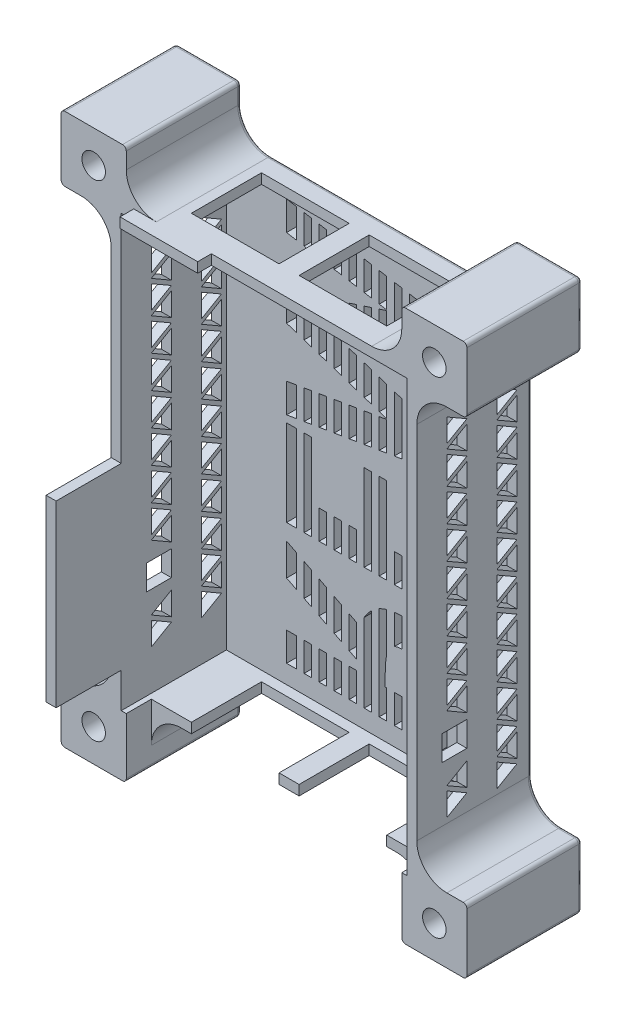
SolidWorks part; units mm, degrees
ref_plane "Front Plane" through (0, 0, 0) normal (0, 0, 1) x (1, 0, 0)
ref_plane "Top Plane" through (0, 0, 0) normal (0, 1, 0) x (1, 0, 0)
ref_plane "Right Plane" through (0, 0, 0) normal (1, 0, 0) x (0, 0, -1)
sketch "Sketch1" plane through (0, 0, 0) normal (0, 0, 1) x (1, 0, 0)
  line L1 (0, 0) -> (61, 0)
  line L2 (0, 0) -> (0, 90)
  line L3 (0, 90) -> (61, 90)
  line L4 (61, 0) -> (61, 90)
  dimension "D1" = 90
  dimension "D2" = 61
extrude "Boss-Extrude1" add sketch "Sketch1" along normal blind 4
sketch "Sketch2" plane through (0, 0, 4) normal (0, 0, 1) x (1, 0, 0)
  line L0 (61, 90) -> (0, 90) construction
  line L1 (2, 88) -> (59, 88)
  line L2 (2, 88) -> (2, 2)
  line L3 (2, 2) -> (59, 2)
  line L4 (59, 88) -> (59, 2)
  line L5 (2.2, 0) -> (-2.2, 0) construction
  line L6 (0, -2.2) -> (0, 2.2) construction
  line L7 (61, 0) -> (61, 90) construction
  dimension "D1" = 2
  dimension "D2" = 2
  dimension "D3" = 2
  dimension "D4" = 2
extrude "Cut-Extrude1" cut sketch "Sketch2" against normal blind 2
sketch "Sketch3" plane through (0, 0, 4) normal (0, 0, 1) x (1, 0, 0)
  line L8 (2, 88) -> (2, 2)
  line L9 (2, 2) -> (59, 2)
  line L10 (59, 2) -> (59, 88)
  line L11 (59, 88) -> (2, 88)
  line L12 (2, 88) -> (2, 2)
  line L13 (2, 2) -> (59, 2)
  line L14 (59, 2) -> (59, 88)
  line L15 (59, 88) -> (2, 88)
  line L26 (0, 90) -> (0, 0)
  line L27 (0, 0) -> (61, 0)
  line L28 (61, 0) -> (61, 90)
  line L29 (61, 90) -> (0, 90)
  line L30 (0, 90) -> (0, 0)
  line L31 (0, 0) -> (61, 0)
  line L32 (61, 0) -> (61, 90)
  line L33 (61, 90) -> (0, 90)
  dimension "D1" = 2
  dimension "D2" = 0
extrude "Boss-Extrude2" add sketch "Sketch3" along normal blind 14
sketch "Sketch4" plane through (0, 0, 18) normal (0, 0, 1) x (1, 0, 0)
  line L2 (9.9, 0) -> (-9.9, 0) construction
  line L3 (0, -9.9) -> (0, 9.9) construction
  line L4 (61, 0) -> (61, 90) construction
  line L10 (0, 90) -> (0, 0) construction
  line L12 (2, 88) -> (2, 2) construction
  line L13 (2, 88) -> (2, 2) construction
  line L14 (2, 2) -> (2, 88)
  line L15 (59, 88) -> (2, 88) construction
  line L16 (59, 88) -> (2, 88) construction
  line L49 (59, 88) -> (2, 88)
  line L50 (59, 2) -> (59, 88)
  line L52 (0, 90) -> (0, 2)
  line L53 (61, 90) -> (0, 90)
  line L54 (61, 2) -> (61, 90)
  line L55 (59, 2) -> (61, 2)
  line L56 (2, 2) -> (0, 2)
  dimension "D2" = 2
  dimension "D3" = 2
  dimension "D1" = 2
extrude "Boss-Extrude3" add sketch "Sketch4" along normal blind 5
sketch "Sketch5" plane through (0, 0, 0) normal (0, -1, 0) x (-1, 0, 0)
  line L0 (0, -18) -> (-61, -18) construction
  line L1 (-11, -18) -> (-28.5, -18)
  line L2 (-11, -18) -> (-11, -4)
  line L3 (-11, -4) -> (-28.5, -4)
  line L4 (-28.5, -18) -> (-28.5, -4)
  line L5 (0, 9.9) -> (0, -9.9) construction
  line L6 (-32.5, -18) -> (-50, -18)
  line L7 (-32.5, -18) -> (-32.5, -4)
  line L8 (-32.5, -4) -> (-50, -4)
  line L9 (-50, -18) -> (-50, -4)
  dimension "D1" = 14
  dimension "D2" = 14
  dimension "D3" = 17.5
  dimension "D4" = 17.5
  dimension "D5" = 4
  dimension "D6" = 11
extrude "Cut-Extrude2" cut sketch "Sketch5" against normal blind 5
sketch "Sketch6" plane through (0, 90, 0) normal (0, 1, 0) x (1, 0, 0)
  line L2 (50, -18) -> (50, -4)
  line L3 (50, -4) -> (32.5, -4)
  line L4 (32.5, -18) -> (32.5, -4)
  line L5 (61, 0) -> (0, 0) construction
  line L7 (28.5, -18) -> (28.5, -4)
  line L8 (28.5, -4) -> (11, -4)
  line L9 (11, -18) -> (11, -4)
  line L10 (61, -23) -> (61, 0) construction
  line L12 (11, -18) -> (28.5, -18)
  line L13 (32.5, -18) -> (50, -18)
  dimension "D1" = 4
  dimension "D2" = 4
  dimension "D3" = 4
  dimension "D4" = 17.5
  dimension "D5" = 17.5
  dimension "D6" = 11
  dimension "D7" = 14
  dimension "D8" = 14
extrude "Cut-Extrude3" cut sketch "Sketch6" against normal blind 5
sketch "Sketch7" plane through (0, 0, 23) normal (0, 0, 1) x (1, 0, 0)
  line L0 (0, 90) -> (0, 2) construction
  line L1 (0, 9) -> (2, 9)
  line L2 (0, 9) -> (0, 44.75)
  line L3 (0, 44.75) -> (2, 44.75)
  line L4 (2, 9) -> (2, 44.75)
  line L5 (2, 2) -> (2, 88) construction
  line L6 (0, 2) -> (2, 2) construction
  dimension "D1" = 7
  dimension "D2" = 35.75
extrude "Boss-Extrude4" add sketch "Sketch7" along normal blind 13
sketch "Sketch8" plane through (61, 0, 0) normal (1, 0, 0) x (0, 0, -1)
  line L0 (-13, 17.852) -> (-13, 13.2332)
  line L5 (-13, 13.2332) -> (-17, 15.5426)
  line L6 (-17, 15.5426) -> (-13, 17.852)
  line L8 (-13, 20) -> (-18, 20)
  line L9 (-13, 20) -> (-13, 25)
  line L10 (-13, 25) -> (-18, 25)
  line L11 (-18, 20) -> (-18, 25)
  line L23 (-18, 0) -> (0, 0) construction
  line L24 (0, 0) -> (0, 90) construction
  line L25 (-3, 12.3094) -> (-7, 10)
  line L26 (-7, 10) -> (-7, 14.6188)
  line L27 (-7, 14.6188) -> (-3, 12.3094)
  line L28 (-3, 13.2332) -> (-7, 15.5426)
  line L29 (-7, 15.5426) -> (-3, 17.852)
  line L30 (-3, 17.852) -> (-3, 13.2332)
  line L31 (-17, 14.6188) -> (-13, 12.3094)
  line L32 (-13, 12.3094) -> (-17, 10)
  line L33 (-17, 10) -> (-17, 14.6188)
  line L40 (-13, 30.7846) -> (-13, 26.1658)
  line L41 (-13, 26.1658) -> (-17, 28.4752)
  line L42 (-17, 28.4752) -> (-13, 30.7846)
  line L46 (-13, 37.2509) -> (-13, 32.6321)
  line L47 (-13, 32.6321) -> (-17, 34.9415)
  line L48 (-17, 34.9415) -> (-13, 37.2509)
  line L49 (-17, 34.0178) -> (-13, 31.7084)
  line L50 (-13, 31.7084) -> (-17, 29.399)
  line L51 (-17, 29.399) -> (-17, 34.0178)
  line L52 (-13, 43.7173) -> (-13, 39.0985)
  line L53 (-13, 39.0985) -> (-17, 41.4079)
  line L54 (-17, 41.4079) -> (-13, 43.7173)
  line L55 (-17, 40.4841) -> (-13, 38.1747)
  line L56 (-13, 38.1747) -> (-17, 35.8653)
  line L57 (-17, 35.8653) -> (-17, 40.4841)
  line L58 (-13, 50.1836) -> (-13, 45.5648)
  line L59 (-13, 45.5648) -> (-17, 47.8742)
  line L60 (-17, 47.8742) -> (-13, 50.1836)
  line L61 (-17, 46.9504) -> (-13, 44.641)
  line L62 (-13, 44.641) -> (-17, 42.3316)
  line L63 (-17, 42.3316) -> (-17, 46.9504)
  line L64 (-13, 56.6499) -> (-13, 52.0311)
  line L65 (-13, 52.0311) -> (-17, 54.3405)
  line L66 (-17, 54.3405) -> (-13, 56.6499)
  line L67 (-17, 53.4167) -> (-13, 51.1073)
  line L68 (-13, 51.1073) -> (-17, 48.7979)
  line L69 (-17, 48.7979) -> (-17, 53.4167)
  line L70 (-13, 63.1162) -> (-13, 58.4974)
  line L71 (-13, 58.4974) -> (-17, 60.8068)
  line L72 (-17, 60.8068) -> (-13, 63.1162)
  line L73 (-17, 59.8831) -> (-13, 57.5737)
  line L74 (-13, 57.5737) -> (-17, 55.2643)
  line L75 (-17, 55.2643) -> (-17, 59.8831)
  line L76 (-13, 69.5825) -> (-13, 64.9637)
  line L77 (-13, 64.9637) -> (-17, 67.2731)
  line L78 (-17, 67.2731) -> (-13, 69.5825)
  line L79 (-17, 66.3494) -> (-13, 64.04)
  line L80 (-13, 64.04) -> (-17, 61.7306)
  line L81 (-17, 61.7306) -> (-17, 66.3494)
  line L82 (-13, 76.0489) -> (-13, 71.4301)
  line L83 (-13, 71.4301) -> (-17, 73.7395)
  line L84 (-17, 73.7395) -> (-13, 76.0489)
  line L85 (-17, 72.8157) -> (-13, 70.5063)
  line L86 (-13, 70.5063) -> (-17, 68.1969)
  line L87 (-17, 68.1969) -> (-17, 72.8157)
  line L91 (-17, 79.282) -> (-13, 76.9726)
  line L92 (-13, 76.9726) -> (-17, 74.6632)
  line L93 (-17, 74.6632) -> (-17, 79.282)
  line L94 (-3, 24.3183) -> (-3, 19.6995)
  line L95 (-3, 19.6995) -> (-7, 22.0089)
  line L96 (-7, 22.0089) -> (-3, 24.3183)
  line L97 (-7, 21.0851) -> (-3, 18.7757)
  line L98 (-3, 18.7757) -> (-7, 16.4663)
  line L99 (-7, 16.4663) -> (-7, 21.0851)
  line L100 (-3, 30.7846) -> (-3, 26.1658)
  line L101 (-3, 26.1658) -> (-7, 28.4752)
  line L102 (-7, 28.4752) -> (-3, 30.7846)
  line L103 (-7, 27.5514) -> (-3, 25.242)
  line L104 (-3, 25.242) -> (-7, 22.9326)
  line L105 (-7, 22.9326) -> (-7, 27.5514)
  line L106 (-3, 37.2509) -> (-3, 32.6321)
  line L107 (-3, 32.6321) -> (-7, 34.9415)
  line L108 (-7, 34.9415) -> (-3, 37.2509)
  line L109 (-7, 34.0178) -> (-3, 31.7084)
  line L110 (-3, 31.7084) -> (-7, 29.399)
  line L111 (-7, 29.399) -> (-7, 34.0178)
  line L112 (-3, 43.7173) -> (-3, 39.0985)
  line L113 (-3, 39.0985) -> (-7, 41.4079)
  line L114 (-7, 41.4079) -> (-3, 43.7173)
  line L115 (-7, 40.4841) -> (-3, 38.1747)
  line L116 (-3, 38.1747) -> (-7, 35.8653)
  line L117 (-7, 35.8653) -> (-7, 40.4841)
  line L118 (-3, 50.1836) -> (-3, 45.5648)
  line L119 (-3, 45.5648) -> (-7, 47.8742)
  line L120 (-7, 47.8742) -> (-3, 50.1836)
  line L121 (-7, 46.9504) -> (-3, 44.641)
  line L122 (-3, 44.641) -> (-7, 42.3316)
  line L123 (-7, 42.3316) -> (-7, 46.9504)
  line L124 (-3, 56.6499) -> (-3, 52.0311)
  line L125 (-3, 52.0311) -> (-7, 54.3405)
  line L126 (-7, 54.3405) -> (-3, 56.6499)
  line L127 (-7, 53.4167) -> (-3, 51.1073)
  line L128 (-3, 51.1073) -> (-7, 48.7979)
  line L129 (-7, 48.7979) -> (-7, 53.4167)
  line L130 (-3, 63.1162) -> (-3, 58.4974)
  line L131 (-3, 58.4974) -> (-7, 60.8068)
  line L132 (-7, 60.8068) -> (-3, 63.1162)
  line L133 (-7, 59.8831) -> (-3, 57.5737)
  line L134 (-3, 57.5737) -> (-7, 55.2643)
  line L135 (-7, 55.2643) -> (-7, 59.8831)
  line L136 (-3, 69.5825) -> (-3, 64.9637)
  line L137 (-3, 64.9637) -> (-7, 67.2731)
  line L138 (-7, 67.2731) -> (-3, 69.5825)
  line L139 (-7, 66.3494) -> (-3, 64.04)
  line L140 (-3, 64.04) -> (-7, 61.7306)
  line L141 (-7, 61.7306) -> (-7, 66.3494)
  line L142 (-3, 76.0489) -> (-3, 71.4301)
  line L143 (-3, 71.4301) -> (-7, 73.7395)
  line L144 (-7, 73.7395) -> (-3, 76.0489)
  line L145 (-7, 72.8157) -> (-3, 70.5063)
  line L146 (-3, 70.5063) -> (-7, 68.1969)
  line L147 (-7, 68.1969) -> (-7, 72.8157)
  line L151 (-7, 79.282) -> (-3, 76.9726)
  line L152 (-3, 76.9726) -> (-7, 74.6632)
  line L153 (-7, 74.6632) -> (-7, 79.282)
  line L154 (-13, 18.7757) -> (-17, 16.4663) [skipped]
  line L155 (-17, 21.0851) -> (-15.1205, 20) [skipped]
  line L156 (-17, 20) -> (-17, 21.0851) [skipped]
  line L157 (-17, 22.0089) -> (-13, 24.3183) [skipped]
  line L158 (-13, 19.6995) -> (-13.5205, 20) [skipped]
  line L159 (-17, 27.5514) -> (-13, 25.242) [skipped]
  line L160 (-13, 25.242) -> (-13.4192, 25) [skipped]
  line L161 (-17, 25) -> (-17, 27.5514) [skipped]
  line L162 (-13, 18.7757) -> (-13, 17.5514) [skipped]
  line L163 (-13, 82.5152) -> (-13, 77.8964) [skipped]
  line L164 (-17, 80.2058) -> (-13, 82.5152) [skipped]
  line L165 (-13, 77.8964) -> (-17, 80.2058) [skipped]
  line L166 (-7, 80.2058) -> (-3, 82.5152) [skipped]
  line L167 (-3, 77.8964) -> (-7, 80.2058) [skipped]
  line L168 (-3, 82.5152) -> (-3, 77.8964) [skipped]
  dimension "D1" = 20
  dimension "D2" = 60
  dimension "D3" = 60
  dimension "D4" = 4
  dimension "D5" = 5
  dimension "D6" = 5
  dimension "D7" = 13
  dimension "D8" = 0.9238
  dimension "D9" = 10
  dimension "D10" = 3
  dimension "D11" = 60
  dimension "D12" = 2
  dimension "D13" = 11
  dimension "D14" = 0.9238
  dimension "D15" = 17
extrude "Cut-Extrude4" cut sketch "Sketch8" against normal through all
sketch "Sketch9" plane through (-13.2665, 62.4944, 0) normal (0, 0, -1) x (0, 1, 0)
  line L2 (-42.6944, 13.2665) -> (-82.2944, 13.2665) construction
  line L3 (-62.4944, -6.5335) -> (-62.4944, 33.0665) construction
  text T0 "REM" font "Century Gothic" height 32
  dimension "D1" = 14
  dimension "D2" = 2
extrude "Cut-Extrude5" cut sketch "Sketch9" against normal blind 2
sketch "Sketch16" plane through (0, 0, 23) normal (0, 0, 1) x (1, 0, 0)
  line L0 (2, 88) -> (59, 88) construction
  line L1 (20, 88) -> (4.5, 88)
  line L2 (20, 88) -> (20, 90)
  line L3 (20, 90) -> (4.5, 90)
  line L4 (4.5, 88) -> (4.5, 90)
  line L5 (61, 90) -> (0, 90) construction
  line L6 (0, 90) -> (0, 61) construction
  dimension "D1" = 4.5
  dimension "D2" = 15.5
extrude "Boss-Extrude9" add sketch "Sketch16" along normal blind 2.75
ref_plane "Plane1" through (2, 14.6188, 17) normal (0, 1, 0) x (1, 0, 0)
sketch "Sketch22" plane through (0, 0, 0) normal (0, 0, -1) x (-1, 0, 0)
  line L0 (-14, 85.9795) -> (-14, 80.1654) construction
  line L1 (-26.5, 0) -> (-25, 0)
  line L2 (0, 0) -> (-61, 0) construction
  line L3 (-61, 90) -> (0, 90) construction
  line L4 (-28, 0) -> (-28, 90)
  line L5 (-28, 90) -> (-29.5, 90)
  line L6 (-29.5, 90) -> (-29.5, 0)
  line L7 (-29.5, 0) -> (-28, 0)
  line L8 (-25, 0) -> (-25, 90)
  line L9 (-25, 90) -> (-26.5, 90)
  line L10 (-26.5, 90) -> (-26.5, 0)
  line L11 (-23.5, 0) -> (-22, 0)
  line L12 (-22, 0) -> (-22, 90)
  line L13 (-22, 90) -> (-23.5, 90)
  line L14 (-23.5, 90) -> (-23.5, 0)
  line L15 (-20.5, 0) -> (-19, 0)
  line L16 (-19, 0) -> (-19, 90)
  line L17 (-19, 90) -> (-20.5, 90)
  line L18 (-20.5, 90) -> (-20.5, 0)
  line L19 (-17.5, 0) -> (-16, 0)
  line L20 (-16, 0) -> (-16, 90)
  line L21 (-16, 90) -> (-17.5, 90)
  line L22 (-17.5, 90) -> (-17.5, 0)
  line L23 (-32.5, 0) -> (-31, 0)
  line L24 (-31, 0) -> (-31, 90)
  line L25 (-31, 90) -> (-32.5, 90)
  line L26 (-32.5, 90) -> (-32.5, 0)
  line L27 (-35.5, 0) -> (-34, 0)
  line L28 (-34, 0) -> (-34, 90)
  line L29 (-34, 90) -> (-35.5, 90)
  line L30 (-35.5, 90) -> (-35.5, 0)
  line L31 (-38.5, 0) -> (-37, 0)
  line L32 (-37, 0) -> (-37, 90)
  line L33 (-37, 90) -> (-38.5, 90)
  line L34 (-38.5, 90) -> (-38.5, 0)
  line L35 (-41.5, 0) -> (-40, 0)
  line L36 (-40, 0) -> (-40, 90)
  line L37 (-40, 90) -> (-41.5, 90)
  line L38 (-41.5, 90) -> (-41.5, 0)
  line L39 (-44.5, 0) -> (-43, 0)
  line L40 (-43, 0) -> (-43, 90)
  line L41 (-43, 90) -> (-44.5, 90)
  line L42 (-44.5, 90) -> (-44.5, 0)
  line L43 (-47.5, 0) -> (-46, 0)
  line L44 (-46, 0) -> (-46, 90)
  line L45 (-46, 90) -> (-47.5, 90)
  line L46 (-47.5, 90) -> (-47.5, 0)
  line L47 (-50.5, 0) -> (-49, 0)
  line L48 (-49, 0) -> (-49, 90)
  line L49 (-49, 90) -> (-50.5, 90)
  line L50 (-50.5, 90) -> (-50.5, 0)
  dimension "D2" = 1.5
  dimension "D4" = 1.5
  dimension "D6" = 1.5
  dimension "D1" = 2
  dimension "D3" = 5
  dimension "D5" = 8
extrude "Boss-Extrude11" add sketch "Sketch22" against normal up to surface (2 mm away) up to face at (36.3205, 13.9436, 2)
fillet "Fillet5" radius 0.75 8 edges at (30.5, 90, 0) (0, 90, 11.5) (30.5, 0, 0) (0, 45, 0) (0, 0, 9) (61, 90, 11.5) (61, 0, 9) (61, 45, 0)
sketch "Sketch36" plane through (0, 0, 0) normal (0, 0, -1) x (-1, 0, 0)
  line L0 (-61, 0.75) -> (-61, 89.25) construction
  line L1 (-58, 3) -> (-71, 3)
  line L2 (-58, 3) -> (-58, -10)
  line L3 (-58, -10) -> (-71, -10)
  line L4 (-71, 3) -> (-71, -10)
  line L5 (-58, 3) -> (-71, -10) construction
  line L6 (-58, -10) -> (-71, 3) construction
  line L8 (-0.75, 0) -> (-60.25, 0) construction
  point P4 (-64.5, -3.5)
  dimension "D1" = 13
  dimension "D2" = 13
  dimension "D3" = 3
  dimension "D4" = 3
extrude "Boss-Extrude13" add sketch "Sketch36" against normal up to surface (23 mm away) up to face at (48.6293, 64.2008, 23)
sketch "Sketch37" plane through (0, 0, 0) normal (0, 0, -1) x (-1, 0, 0)
  line L0 (-60.25, 90) -> (-0.75, 90) construction
  line L1 (-3, 87) -> (10, 87)
  line L2 (-3, 87) -> (-3, 100)
  line L3 (-3, 100) -> (10, 100)
  line L4 (10, 87) -> (10, 100)
  line L5 (-3, 87) -> (10, 100) construction
  line L6 (-3, 100) -> (10, 87) construction
  line L7 (0, 89.25) -> (0, 0.75) construction
  point P4 (3.5, 93.5)
  dimension "D1" = 13
  dimension "D2" = 3
  dimension "D3" = 3
extrude "Boss-Extrude14" add sketch "Sketch37" against normal up to surface (23 mm away) up to face at (1.9421, 76.415, 23)
sketch "Sketch41" plane through (0, 0, 23) normal (0, 0, 1) x (1, 0, 0)
  line L9 (58, 3) -> (59, 3)
  line L10 (58, 3) -> (58, 2)
  line L11 (58, 2) -> (59, 2)
  line L12 (59, 3) -> (59, 2)
  line L13 (58, 3) -> (59, 2) construction
  line L14 (58, 2) -> (59, 3) construction
  line L15 (3, 87) -> (2, 87)
  line L16 (3, 87) -> (3, 88)
  line L17 (3, 88) -> (2, 88)
  line L18 (2, 87) -> (2, 88)
  line L19 (3, 87) -> (2, 88) construction
  line L20 (3, 88) -> (2, 87) construction
  point P13 (58.5, 2.5)
  point P15 (2.5, 87.5)
  dimension "D1" = 1
  dimension "D2" = 1
  dimension "D3" = 1
  dimension "D4" = 1
extrude "Cut-Extrude13" cut sketch "Sketch41" against normal up to surface (21 mm away) up to face at (30.5, 45, 2)
sketch "Sketch46" plane through (0, 0, 0) normal (0, 0, -1) x (-1, 0, 0)
  line L0 (3.5, 100) -> (3.5, 87) construction
  line L1 (10, 100) -> (-3, 100) construction
  line L2 (-0.75, 87) -> (10, 87) construction
  line L3 (10, 93.5) -> (-3, 93.5) construction
  line L4 (10, 87) -> (10, 100) construction
  line L5 (-71, -3.5) -> (-58, -3.5) construction
  line L6 (-71, 3) -> (-71, -10) construction
  line L7 (-58, -10) -> (-58, 0.75) construction
  line L8 (-64.5, -10) -> (-64.5, 3) construction
  line L9 (-71, -10) -> (-58, -10) construction
  line L10 (-60.25, 3) -> (-71, 3) construction
  line L11 (-3, 100) -> (-3, 89.25) construction
  circle A0 centre (-64.5, -3.5) radius 2.35
  circle A1 centre (3.5, 93.5) radius 2.35
  dimension "D1" = 4.7
  dimension "D2" = 4.7
sketch "Sketch49" plane through (0, 0, 0) normal (0, 0, -1) x (-1, 0, 0)
  line L0 (-60.25, 89.25) -> (-60.25, 3) construction
  line L1 (-61, 3) -> (-60.25, 3)
  line L2 (-61, 3) -> (-61, 90)
  line L3 (-61, 90) -> (-60.25, 90)
  line L4 (-60.25, 3) -> (-60.25, 90)
  line L5 (-61, 3) -> (-60.25, 90) construction
  line L6 (-61, 90) -> (-60.25, 3) construction
  line L7 (-60.25, 90) -> (-3, 90)
  line L8 (-60.25, 90) -> (-60.25, 89.25)
  line L9 (-60.25, 89.25) -> (-3, 89.25)
  line L10 (-3, 90) -> (-3, 89.25)
  line L11 (-60.25, 90) -> (-3, 89.25) construction
  line L12 (-60.25, 89.25) -> (-3, 90) construction
  line L13 (-0.75, 87) -> (0, 87)
  line L14 (-0.75, 87) -> (-0.75, 0)
  line L15 (-0.75, 0) -> (0, 0)
  line L16 (0, 87) -> (0, 0)
  line L17 (-0.75, 87) -> (0, 0) construction
  line L18 (-0.75, 0) -> (0, 87) construction
  line L19 (-0.75, 0) -> (-58, 0)
  line L20 (-0.75, 0) -> (-0.75, 0.75)
  line L21 (-0.75, 0.75) -> (-58, 0.75)
  line L22 (-58, 0) -> (-58, 0.75)
  line L23 (-0.75, 0) -> (-58, 0.75) construction
  line L24 (-0.75, 0.75) -> (-58, 0) construction
  arc A0 (-60.25, 90) -> (-61, 89.25) centre (-60.25, 89.25) ccw construction
  point P4 (-60.625, 46.5)
  point P12 (-31.625, 89.625)
  point P18 (-0.375, 43.5)
  point P24 (-29.375, 0.375)
extrude "Boss-Extrude15" add sketch "Sketch49" against normal blind 1 contours L2 L1 L4 L3 | L20 L19 L22 L21 | L14 L13 L16 L15 | L8 L7 L10 L9
fillet "Fillet8" radius 6 1 edges at (61, 3, 11.5) type face fillet first side face at (61, 73.7395, 14.3333) second side face at (66, 3, 11.5) tangent propagation no
fillet "Fillet9" radius 6 1 edges at (58, 0, 9) type face fillet first side face at (58, -2.6667, 13.6667) second side face at (25.8214, 0, 9) tangent propagation no
fillet "Fillet10" radius 6 1 edges at (3, 90, 11.5) type face fillet first side face at (29.75, 90, 14.55) second side face at (3, 95, 11.5) tangent propagation no
fillet "Fillet11" radius 6 1 edges at (0, 87, 11.5) type face fillet first side face at (0, 73.7395, 14.3333) second side face at (-5, 87, 11.5) tangent propagation no
extrude "Cut-Extrude18" cut sketch "Sketch46" against normal through all
sketch "Sketch50" plane through (0, 90, 0) normal (0, 1, 0) x (1, 0, 0)
  line L0 (20, -25.75) -> (9, -25.75) construction
  line L1 (4.5, -23) -> (10, -23)
  line L2 (4.5, -23) -> (4.5, -25.75)
  line L3 (4.5, -25.75) -> (10, -25.75)
  line L4 (10, -23) -> (10, -25.75)
  line L5 (4.5, -23) -> (10, -25.75) construction
  line L6 (4.5, -25.75) -> (10, -23) construction
  point P4 (7.25, -24.375)
  dimension "D1" = 5.5
extrude "Cut-Extrude19" cut sketch "Sketch50" along normal through all
sketch "Sketch51" plane through (0, 0, 23) normal (0, 0, 1) x (1, 0, 0)
  line L0 (61, 9) -> (61, 89.25) construction
  line L1 (-10, -10) -> (3, -10)
  line L2 (-10, -10) -> (-10, 3)
  line L3 (-10, 3) -> (2, 3)
  line L4 (3, -10) -> (3, 2)
  line L5 (-10, -10) -> (2, 2) construction
  line L6 (-10, 3) -> (3, -10) construction
  line L7 (59, 87) -> (71, 87)
  line L8 (58, 88) -> (58, 100)
  line L9 (58, 100) -> (71, 100)
  line L10 (71, 87) -> (71, 100)
  line L11 (59, 88) -> (71, 100) construction
  line L12 (58, 100) -> (71, 87) construction
  line L13 (60.25, 90) -> (20, 90) construction
  line L14 (0.75, 0) -> (11, 0) construction
  line L15 (0, 44.75) -> (0, 9) construction
  line L16 (2, 2) -> (11, 2) construction
  line L17 (2, 2) -> (2, 9) construction
  line L18 (2, 2) -> (3, 2)
  line L19 (2, 2) -> (2, 3)
  line L20 (59, 88) -> (59, 2) construction
  line L21 (59, 88) -> (2, 88) construction
  line L22 (59, 88) -> (59, 87)
  line L23 (59, 88) -> (58, 88)
  point P4 (-3.5, -3.5)
  point P9 (64.5, 93.5)
  dimension "D1" = 3
  dimension "D2" = 3
  dimension "D3" = 3
  dimension "D4" = 3
  dimension "D5" = 13
  dimension "D6" = 13
  dimension "D7" = 13
  dimension "D8" = 13
extrude "Boss-Extrude16" add sketch "Sketch51" against normal up to surface (23 mm away) contours L1 L4 L18 L19 L3 L2 | L7 L10 L9 L8 L23 L22 up to face at (62.15, -3.5, 0)
sketch "Sketch52" plane through (0, 0, 0) normal (0, 0, -1) x (-1, 0, 0)
  line L0 (-64.5, 100) -> (-64.5, 87) construction
  line L1 (-58, 100) -> (-71, 100) construction
  line L2 (-61, 87) -> (-71, 87) construction
  line L3 (-71, 93.5) -> (-58, 93.5) construction
  line L4 (-71, 87) -> (-71, 100) construction
  line L5 (-58, 90) -> (-58, 100) construction
  line L6 (3.5, -10) -> (3.5, 3) construction
  line L7 (10, -10) -> (-3, -10) construction
  line L8 (10, 3) -> (0, 3) construction
  line L9 (10, -3.5) -> (-3, -3.5) construction
  line L10 (10, -10) -> (10, 3) construction
  line L11 (-3, -10) -> (-3, 0) construction
  circle A0 centre (-64.5, 93.5) radius 2.35
  circle A1 centre (3.5, -3.5) radius 2.35
  dimension "D1" = 4.7
  dimension "D2" = 4.7
extrude "Cut-Extrude20" cut sketch "Sketch52" against normal through all
fillet "Fillet13" radius 6 1 edges at (58, 90, 11.5) type face fillet first side face at (58, 95, 11.5) second side face at (41.25, 90, 11) tangent propagation no
fillet "Fillet14" radius 6 1 edges at (61, 87, 11.5) type face fillet first side face at (66, 87, 11.5) second side face at (61, 73.7395, 14.3333) tangent propagation no
fillet "Fillet15" radius 6 1 edges at (3, 0, 9) type face fillet first side face at (29.5, 0, 10.3333) second side face at (3, -2.6667, 13.6667) tangent propagation no
fillet "Fillet16" radius 6 1 edges at (0, 3, 11.5) type face fillet first side face at (-5, 3, 11.5) second side face at (0, 12.3094, 5.6667) tangent propagation no
fillet "Fillet18" radius 0.75 40 edges at (58, 98, 0) (56.2426, 91.7574, 0) (30.5, 90, 0) (3, 98, 0) (-8, 87, 0) (-1.7574, 85.2426, 0) (-8, 3, 0) (-1.7574, 4.7574, 0) (69, 3, 0) (69, 87, 0) (62.7574, 85.2426, 0) (61, 45, 0) (3, -8, 0) (4.7574, -1.7574, 0) (30.5, 0, 0) (58, -8, 0) (3, 100, 11.5) (71, 87, 11.5) (71, 100, 11.5) (58, 100, 11.5) (71, 3, 11.5) (4.7574, 91.7574, 0) (-3.5, 100, 0) (-10, 100, 11.5) (-10, 93.5, 0) (-10, 87, 11.5) (0, 45, 0) (-10, 3, 11.5) (-10, -3.5, 0) (-3.5, -10, 0) (-10, -10, 11.5) (3, -10, 11.5) (58, -10, 11.5) (71, -10, 11.5) (64.5, -10, 0) (71, -3.5, 0) (62.7574, 4.7574, 0) (56.2426, -1.7574, 0) (71, 93.5, 0) (64.5, 100, 0)
equation "\"A\"= 1.5mm"
equation "\"B\"= 1.5mm"
equation "\"D2@Sketch22\"=\"A\""
